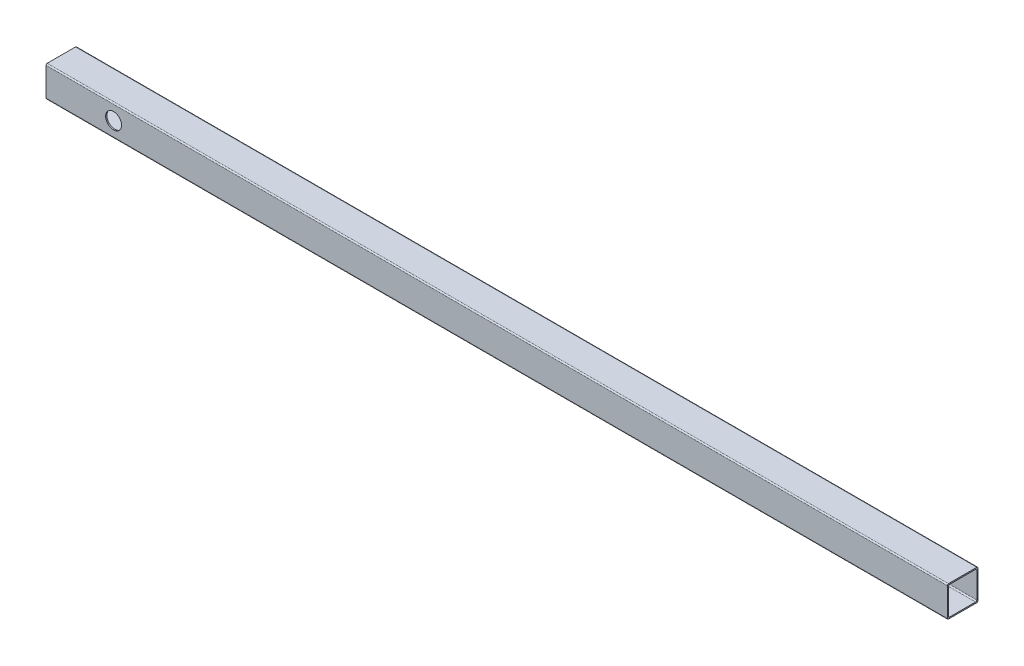
SolidWorks part; units mm, degrees
material "Thornel Mat VMA"
ref_plane "Front Plane" through (0, 0, 0) normal (0, 0, 1) x (1, 0, 0)
ref_plane "Top Plane" through (0, 0, 0) normal (0, 1, 0) x (1, 0, 0)
ref_plane "Right Plane" through (0, 0, 0) normal (1, 0, 0) x (0, 0, -1)
sketch "Sketch2" plane through (0, 0, 0) normal (1, 0, 0) x (0, 0, -1)
  line L1 (0.762, 0) -> (18.288, 0)
  line L2 (0, 0.762) -> (0, 18.288)
  line L3 (0.762, 19.05) -> (18.288, 19.05)
  line L4 (19.05, 0.762) -> (19.05, 18.288)
  line L5 (1.524, 0.762) -> (17.526, 0.762)
  line L6 (0.762, 1.524) -> (0.762, 17.526)
  line L7 (1.524, 18.288) -> (17.526, 18.288)
  line L8 (18.288, 1.524) -> (18.288, 17.526)
  arc A0 (17.526, 18.288) -> (18.288, 17.526) centre (17.526, 17.526) cw
  arc A1 (17.526, 0.762) -> (18.288, 1.524) centre (17.526, 1.524) ccw
  arc A2 (1.524, 0.762) -> (0.762, 1.524) centre (1.524, 1.524) cw
  arc A3 (0.762, 17.526) -> (1.524, 18.288) centre (1.524, 17.526) cw
  arc A4 (18.288, 19.05) -> (19.05, 18.288) centre (18.288, 18.288) cw
  arc A5 (18.288, 0) -> (19.05, 0.762) centre (18.288, 0.762) ccw
  arc A6 (0.762, 0) -> (0, 0.762) centre (0.762, 0.762) cw
  arc A7 (0, 18.288) -> (0.762, 19.05) centre (0.762, 18.288) cw
  point P11 (18.288, 18.288)
  point P14 (18.288, 0.762)
  point P19 (0.762, 18.288)
  point P22 (19.05, 19.05)
  point P25 (19.05, 0)
  point P28 (0, 0)
  point P31 (0, 19.05)
  dimension "D7" = 0.762
  dimension "D1" = 19.05
  dimension "D2" = 19.05
  dimension "D5" = 0.762
  dimension "D6" = 0.762
  dimension "D3" = 0.762
  dimension "D4" = 0.762
extrude "Boss-Extrude1" add sketch "Sketch2" along normal blind 558.8
sketch "Sketch3" plane through (0, 0, 0) normal (0, 0, 1) x (1, 0, 0)
  line L0 (0, 18.288) -> (0, 0.762) construction
  line L1 (558.8, 19.05) -> (0, 19.05) construction
  circle A0 centre (41.91, 9.525) radius 4.953
  dimension "D1" = 9.906
  dimension "D2" = 41.91
  dimension "D3" = 9.525
extrude "Cut-Extrude1" cut sketch "Sketch3" against normal up to surface (19.05 mm away) up to face at (279.4, 9.525, -19.05)
sketch "Sketch4" plane through (558.8, 0, 0) normal (1, 0, 0) x (0, 0, -1)
  line L1 (0, 14.478) -> (0, 4.572)
  line L2 (0, 14.478) -> (0, 4.572)
  line L6 (19.05, 0.762) -> (19.05, 18.288)
  line L7 (0.762, 0) -> (18.288, 0)
  line L8 (0, 18.288) -> (0, 0.762)
  line L9 (18.288, 19.05) -> (0.762, 19.05)
  line L10 (19.05, 0.762) -> (19.05, 18.288)
  line L11 (0.762, 0) -> (18.288, 0)
  line L12 (0, 18.288) -> (0, 0.762)
  line L13 (18.288, 19.05) -> (0.762, 19.05)
  arc A4 (19.05, 18.288) -> (18.288, 19.05) centre (18.288, 18.288) ccw
  arc A5 (18.288, 0) -> (19.05, 0.762) centre (18.288, 0.762) ccw
  arc A6 (0, 0.762) -> (0.762, 0) centre (0.762, 0.762) ccw
  arc A7 (0.762, 19.05) -> (0, 18.288) centre (0.762, 18.288) ccw
  arc A8 (19.05, 18.288) -> (18.288, 19.05) centre (18.288, 18.288) ccw
  arc A9 (18.288, 0) -> (19.05, 0.762) centre (18.288, 0.762) ccw
  arc A10 (0, 0.762) -> (0.762, 0) centre (0.762, 0.762) ccw
  arc A11 (0.762, 19.05) -> (0, 18.288) centre (0.762, 18.288) ccw
  dimension "D1" = 0
  dimension "D2" = 0
equation "\"shaft\"=0.75"
equation "\"D1@Sketch2\"=\"shaft\""
equation "\"D2@Sketch2\"=\"shaft\""
equation "\"IDshaft\"=0.4375"
equation "\"D3@Sketch3\"=\"shaft\"/2"
